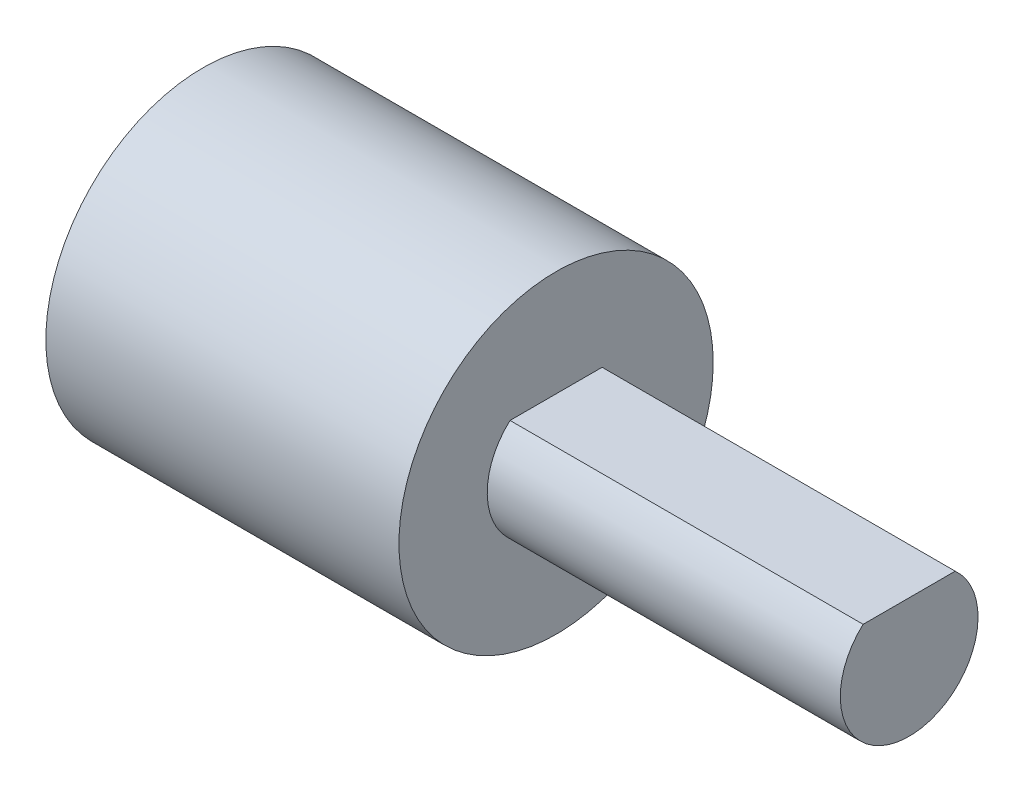
SolidWorks part; units mm, degrees
ref_plane "Front Plane" through (0, 0, 0) normal (0, 0, 1) x (1, 0, 0)
ref_plane "Top Plane" through (0, 0, 0) normal (0, 1, 0) x (1, 0, 0)
ref_plane "Right Plane" through (0, 0, 0) normal (1, 0, 0) x (0, 0, -1)
sketch "Sketch1" plane through (0, 0, 0) normal (1, 0, 0) x (0, 0, -1)
  line L0 (-1.3038, 1.45) -> (1.3038, 1.45)
  circle A0 centre (0, 0) radius 1.95
  circle A1 centre (0, 0) radius 4.45
  dimension "D1" = 3.9
  dimension "D3" = 8.9
  dimension "D2" = 0.5
extrude "Boss-Extrude1" add sketch "Sketch1" along normal blind 10 contours L0 A0 region at (0, -0.1337, 0)
extrude "Boss-Extrude2" add sketch "Sketch1<3>" against normal blind 10 contours A1 A0 | L0 A0 | L0 A0 region at (0, 1.6524, 0) region at (0, -0.1337, 0) region at (0, 0, 4.3241)
sketch "Sketch1<3>" plane through (0, 0, 0) normal (1, 0, 0) x (0, 0, -1) same geometry as "Sketch1"
